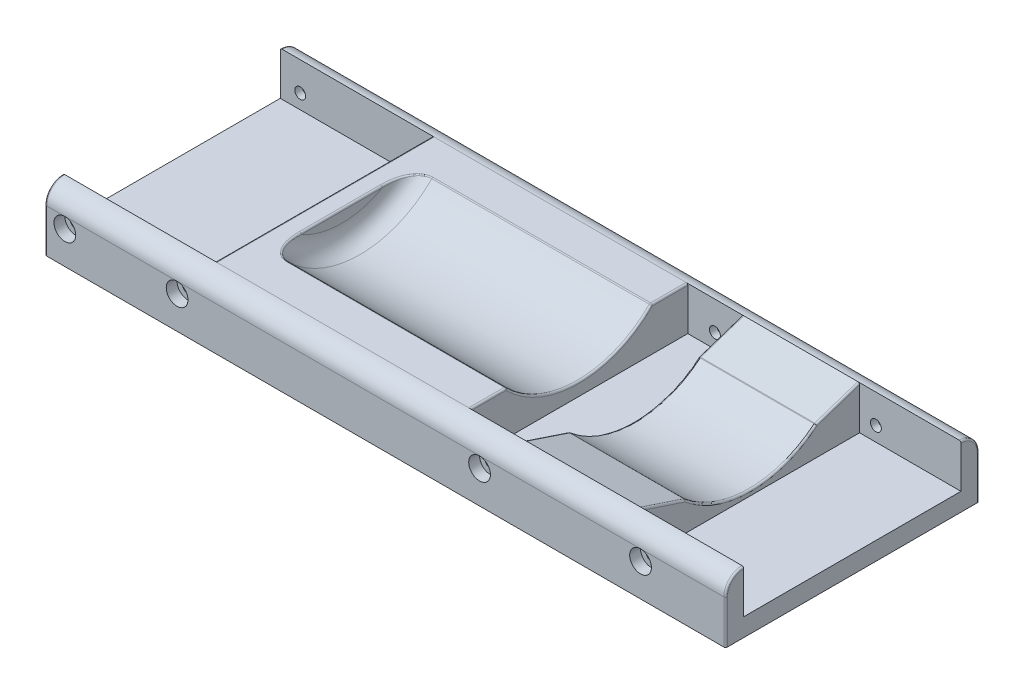
SolidWorks part; units mm, degrees
material "ABS"
ref_plane "Front Plane" through (0, 0, 0) normal (0, 0, 1) x (1, 0, 0)
ref_plane "Top Plane" through (0, 0, 0) normal (0, 1, 0) x (1, 0, 0)
ref_plane "Right Plane" through (0, 0, 0) normal (1, 0, 0) x (0, 0, -1)
other "Configuration Table"
sketch "Sketch2" plane through (0, 0, 0) normal (0, 1, 0) x (1, 0, 0)
  line L1 (-94, -35) -> (94, -35)
  line L2 (-94, -35) -> (-94, 35)
  line L3 (-94, 35) -> (94, 35)
  line L4 (94, -35) -> (94, 35)
  line L5 (-94, -35) -> (94, 35) construction
  line L6 (-94, 35) -> (94, -35) construction
  point P0 (0, 0)
  dimension "D1" = 188
  dimension "D2" = 70
extrude "Boss-Extrude1" add sketch "Sketch2" along normal blind 5
sketch "Sketch3" plane through (0, 5, 0) normal (0, 1, 0) x (1, 0, 0)
  line L0 (94, 0) -> (-94, 0) construction
  line L1 (-94, 35) -> (-94, -35) construction
  line L2 (0, 35) -> (0, -35) construction
  line L3 (-94, -35) -> (94, -35) construction
  point P6 (0, 0)
  point P12 (0, 0)
sketch "Sketch4" plane through (0, 5, 0) normal (0, 1, 0) x (1, 0, 0)
  line L0 (-52, 35) -> (-52, -35) construction
  line L1 (94, 35) -> (-94, 35) construction
  line L2 (-94, -35) -> (94, -35) construction
  line L3 (-94, 35) -> (-94, -35) construction
  line L4 (-68.4393, -29.9983) -> (-68.4393, 29.9983) construction
  line L6 (-47, -35) -> (-94, -35)
  line L7 (-94, 29.9983) -> (-94, 35)
  line L8 (-94, -29.9983) -> (-52, -29.9983)
  line L9 (-52, -29.9983) -> (-52, 29.9983)
  line L10 (-94, -35) -> (-94, -29.9983)
  line L11 (-52, 29.9983) -> (-94, 29.9983)
  line L12 (-47, 35) -> (-47, -35)
  line L13 (-94, 35) -> (-47, 35)
  point P11 (-68.4393, 29.9983)
  point P12 (-68.4393, 0)
  dimension "D1" = 42
  dimension "D2" = 5.0017
  dimension "D3" = 5
extrude "Boss-Extrude2" add sketch "Sketch4" along normal blind 12
sketch "Sketch5" plane through (0, 5, 0) normal (0, 1, 0) x (1, 0, 0)
  line L0 (13.55, 35) -> (13.55, -35)
  line L1 (94, 35) -> (-47, 35) construction
  line L2 (-47, -35) -> (94, -35) construction
  line L4 (18.55, 35) -> (18.55, -35) construction
  line L5 (13.55, 35) -> (33.55, 35)
  line L6 (33.55, 35) -> (33.55, 30)
  line L7 (33.55, 30) -> (18.55, 30)
  line L8 (18.55, 30) -> (18.55, -30)
  line L9 (18.55, -30) -> (33.55, -30)
  line L10 (33.55, -30) -> (33.55, -35)
  line L11 (33.55, -35) -> (13.55, -35)
  line L12 (-47, -35) -> (-47, 35) construction
  dimension "D1" = 65.55
  dimension "D2" = 5
  dimension "D3" = 20
  dimension "D4" = 5
  dimension "D5" = 60
  dimension "D6" = 20
extrude "Boss-Extrude3" add sketch "Sketch5" along normal blind 12
sketch "Sketch6" plane through (13.55, 0, 0) normal (-1, 0, 0) x (0, 0, 1)
  line L6 (20, 17) -> (-20, 17)
  arc A2 (-20, 17) -> (20, 17) centre (0, 36.5959) ccw
  point P3 (-20, 17)
  point P4 (0, 17)
  point P5 (-8.25, 17)
  point P6 (-5.25, 17)
  point P7 (0, 17)
  dimension "D1" = 28
extrude "Cut-Extrude1" cut sketch "Sketch6" against normal blind 5
sketch "Sketch8" plane through (0, 5, 0) normal (0, 1, 0) x (1, 0, 0)
  line L5 (-47, 35) -> (13.55, 35)
  line L6 (-47, 35) -> (-47, 30)
  line L7 (-47, 30) -> (13.55, 30)
  line L8 (13.55, 35) -> (13.55, 30)
  line L9 (13.55, 35) -> (13.55, -35) construction
  line L11 (-47, -35) -> (13.55, -35)
  line L12 (-47, -35) -> (-47, -30)
  line L13 (-47, -30) -> (13.55, -30)
  line L14 (13.55, -35) -> (13.55, -30)
  dimension "D1" = 5
  dimension "D2" = 60.55
  dimension "D3" = 5
  dimension "D4" = 60.55
extrude "Boss-Extrude4" add sketch "Sketch8" along normal blind 12
sketch "Sketch10" plane through (13.55, 0, 0) normal (-1, 0, 0) x (0, 0, 1)
  line L0 (-30, 17) -> (-30, 5)
  line L1 (-30, 5) -> (30, 5)
  line L2 (30, 5) -> (30, 17)
  line L3 (30, 17) -> (20, 17)
  line L4 (-30, 17) -> (-20, 17)
  arc A0 (-20, 17) -> (20, 17) centre (0, 36.5959) ccw
extrude "Boss-Extrude6" add sketch "Sketch10" along normal blind 61.5
sketch "Sketch11" plane through (0, 5, 0) normal (0, 1, 0) x (1, 0, 0)
  line L1 (33.55, 35) -> (94, 35)
  line L2 (33.55, 35) -> (33.55, 30)
  line L3 (33.55, 30) -> (94, 30)
  line L4 (94, 35) -> (94, 30)
  line L5 (94, -35) -> (94, 35) construction
  line L7 (33.55, -30) -> (94, -30)
  line L8 (33.55, -30) -> (33.55, -35)
  line L9 (33.55, -35) -> (94, -35)
  line L10 (94, -30) -> (94, -35)
  dimension "D1" = 5
  dimension "D2" = 60.45
extrude "Boss-Extrude7" add sketch "Sketch11" along normal blind 12
sketch "Sketch14" plane through (0, 5, 0) normal (0, 1, 0) x (1, 0, 0)
  line L0 (18.55, 0) -> (33.55, 0) construction
  line L1 (18.55, -20) -> (18.55, 20) construction
  line L2 (94, 0) -> (-94, 0) construction
  line L3 (33.55, 30) -> (33.55, -30)
  line L4 (18.55, 30) -> (94, 30) construction
  line L5 (94, -30) -> (18.55, -30) construction
  line L6 (94, -30) -> (18.55, -30) construction
  line L7 (33.55, 30) -> (66, 30)
  line L8 (33.55, 30) -> (33.55, -30)
  line L9 (33.55, -30) -> (66, -30)
  line L10 (66, 30) -> (66, -30)
  line M6 (94, 30) -> (18.55, 30)
  line M8 (18.55, -30) -> (94, -30)
  dimension "D1" = 15
  dimension "D2" = 32.45
extrude "Boss-Extrude9" add sketch "Sketch14" along normal blind 8 contours L10 L3 L8 M6 M8 region at (49.775, 5, 0)
sketch "Sketch15" plane through (66, 0, 0) normal (1, 0, 0) x (0, 0, -1)
  line L7 (18, 13) -> (-18, 13)
  line L8 (30, 13) -> (-30, 13) construction
  arc A5 (-18, 13) -> (18, 13) centre (0, 34.4476) ccw
  point P5 (-0.3476, 11.8639)
  point P6 (-0.3476, 11.8639)
  point P7 (0, 13)
  point P8 (0, 13)
  point P9 (0, 13)
  dimension "D1" = 28
extrude "Cut-Extrude3" cut sketch "Sketch15" against normal blind 33
sketch "Sketch17" plane through (66, 0, 0) normal (1, 0, 0) x (0, 0, -1)
  line L0 (-18, 13) -> (-30, 13)
  line L1 (-30, 13) -> (-30, 17)
  line L2 (-30, 17) -> (-18, 13)
  line L3 (30, 13) -> (18, 13)
  line L4 (18, 13) -> (30, 17)
  line L5 (30, 17) -> (30, 13)
  dimension "D1" = 4
extrude "Boss-Extrude10" add sketch "Sketch17" against normal blind 32.45
fillet "Fillet3" radius 5 3 edges at (0, 17, -35) (0, 17, 35) (-47, 8.5959, 0)
fillet "Fillet4" radius 0.5 27 edges at (-47, 17, 0) (-94, 17, -29.9992) (-94, 15.5355, -33.5355) (-94, 17, 29.9992) (-94, 15.5355, 33.5355) (94, 15.5355, -33.5355) (94, 15.5355, 33.5355) (-94, 6, -35) (-94, 6, 35) (94, 6, -35) (94, 6, 35) (66, 15, 24) (66, 6.4476, 0) (66, 15, -24) (-52, 17, 0) (18.55, 17, 25) (18.55, 8.5959, 0) (18.55, 17, -25) (33.55, 15, 24) (33.55, 15, -24) (33.55, 6.4476, 0) (-11.725, 17, 20) (-44.4359, 17, 19.103) (-11.725, 17, -20) (-45.5634, 17, -17.8506) (49.775, 13, 18) (49.775, 13, -18)
sketch "Sketch18" plane through (0, 0, 35) normal (0, 0, 1) x (1, 0, 0)
  line L0 (26.0465, 65) -> (26.0465, 0) construction
  line L1 (-93.5, 0) -> (93.5, 0) construction
  line L2 (72.9965, 65) -> (72.9965, 0) construction
  line L3 (65.9965, 65) -> (79.9965, 65) construction
  line L4 (-57.5, 65) -> (-57.5, 0) construction
  line L5 (-94, 65) -> (-52, 65) construction
  line L6 (-52, 60) -> (-52, 5) construction
  line L7 (-88.5, 65) -> (-88.5, 0) construction
  line L8 (-94, 5) -> (-94, 60) construction
  line L9 (-93.5, 9) -> (93.5, 9) construction
  line L10 (-93.5, 12) -> (-93.5, 0) construction
  line L11 (93.5, 0) -> (93.5, 12) construction
  circle A0 centre (-88.5, 9) radius 1.5
  circle A1 centre (-57.5, 9) radius 1.5
  circle A2 centre (26.0465, 9) radius 1.5
  circle A3 centre (70.5, 9) radius 1.5
  dimension "D4" = 3
  dimension "D5" = 3
  dimension "D6" = 3
  dimension "D7" = 3
  dimension "D1" = 5.5
  dimension "D2" = 5.5
  dimension "D3" = 9
  dimension "D8" = 23
extrude "Cut-Extrude5" cut sketch "Sketch18" against normal blind 75
sketch "Sketch19" plane through (0, 0, 35) normal (0, 0, 1) x (1, 0, 0)
  circle A0 centre (-88.5, 9) radius 3
  circle A1 centre (-57.5, 9) radius 3
  circle A2 centre (26.0465, 9) radius 3
  circle A3 centre (70.5, 9) radius 3
  dimension "D1" = 6
  dimension "D2" = 6
  dimension "D3" = 6
  dimension "D4" = 6
extrude "Cut-Extrude6" cut sketch "Sketch19" against normal blind 3
sketch "Sketch20" plane through (0, 0, -35) normal (0, 0, -1) x (-1, 0, 0)
  circle A0 centre (-70.5, 9) radius 3
  circle A1 centre (-26.0465, 9) radius 3
  circle A2 centre (57.5, 9) radius 3
  circle A3 centre (88.5, 9) radius 3
  dimension "D1" = 6
  dimension "D2" = 6
  dimension "D3" = 6
  dimension "D4" = 6
extrude "Cut-Extrude7" cut sketch "Sketch20" against normal blind 3
